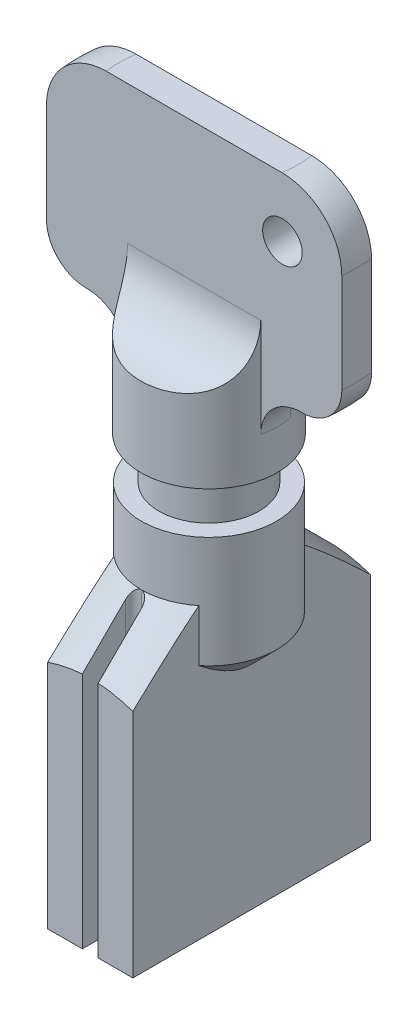
SolidWorks part; units mm, degrees
ref_plane "Front Plane" through (0, 0, 0) normal (0, 0, 1) x (1, 0, 0)
ref_plane "Top Plane" through (0, 0, 0) normal (0, 1, 0) x (1, 0, 0)
ref_plane "Right Plane" through (0, 0, 0) normal (1, 0, 0) x (0, 0, -1)
sketch "Sketch1" plane through (0, 0, 0) normal (0, 0, 1) x (1, 0, 0)
  line L0 (-3.4489, 37.7658) -> (-3.4489, 33.7658)
  line L1 (-3.4489, 33.7658) -> (-2.5348, 33.7658)
  line L2 (-2.5348, 33.7658) -> (-2.5348, 31.625)
  line L3 (-2.5348, 31.625) -> (-3.4177, 31.625)
  line L4 (-3.4177, 31.625) -> (-3.4177, 23)
  line L5 (-3.4177, 23) -> (0, 23)
  line L6 (-3.4489, 37.7658) -> (0, 37.7658)
  line L7 (0, 37.7658) -> (0, 23)
  dimension "D1" = 33.7658
  dimension "D2" = 2.1409
  dimension "D3" = 23
  dimension "D4" = 4
revolve "Revolve1" add sketch "Sketch1" angle 360 about L7
sketch "Sketch2" plane through (0, 37.7658, 0) normal (0, 1, 0) x (1, 0, 0)
  line L1 (-11.4046, 0.75) -> (11.4046, 0.75)
  line L2 (-11.4046, 0.75) -> (-11.4046, -0.75)
  line L3 (-11.4046, -0.75) -> (11.4046, -0.75)
  line L4 (11.4046, 0.75) -> (11.4046, -0.75)
  line L5 (-11.4046, 0.75) -> (11.4046, -0.75) construction
  line L6 (-11.4046, -0.75) -> (11.4046, 0.75) construction
  circle A0 centre (0, 0) radius 3.4489
  circle A1 centre (0, 0) radius 7.5
  circle M3 centre (0, 0) radius 3.4489
  dimension "D2" = 15
  dimension "D1" = 1.5
extrude "Boss-Extrude1" add sketch "Sketch2" along normal blind 10 contours L3 L1 M3 | L1 A1 L3 M3 | L3 A1 L1 M3 region at (-5.4544, 37.7658, 0) region at (0, 37.7658, 0) region at (5.4544, 37.7658, 0)
fillet "Fillet2" radius 2 4 edges at (7.5, 37.7658, 0) (-7.5, 37.7658, 0) (-3.4489, 37.7658, 0) (3.4489, 37.7658, 0)
fillet "Fillet3" radius 3 4 edges at (-7.5, 47.7658, 0) (7.5, 47.7658, 0) (0, 37.7658, -0.75) (0, 37.7658, 0.75)
sketch "Sketch3" plane through (0, 0, 0) normal (0, 0, 1) x (1, 0, 0)
  line L0 (-4.4371, 47.7658) -> (4.4371, 47.7658) construction
  line L1 (7.4624, 44.7658) -> (7.4624, 39.7658) construction
  circle A0 centre (4.4624, 44.7658) radius 1
  dimension "D1" = 2
  dimension "D2" = 3
  dimension "D3" = 3
extrude "Cut-Extrude1" cut sketch "Sketch3" against normal through all and the other way through all
sketch "Sketch4" plane through (0, 0, 0) normal (0, 0, 1) x (1, 0, 0)
  line L1 (0.4, 25.6253) -> (2.15, 25.6253)
  line L2 (0.4, 25.6253) -> (0.4, 14)
  line L3 (0.4, 14) -> (2.15, 14)
  line L4 (2.15, 25.6253) -> (2.15, 14)
  point P4 (4.2262, 13.6459)
  dimension "D1" = 2.15
  dimension "D2" = 0.4
  dimension "D3" = 14
  dimension "D4" = 1.75
extrude "Boss-Extrude2" add sketch "Sketch4" along normal blind 6 and the other way blind 6
chamfer "Chamfer1" distance 3 angle 45 2 edges at (1.3273, 25.6253, -3.1494) (1.3273, 25.6253, 3.1494)
mirror "Mirror2" about plane through (0, 0, 0) normal (1, 0, 0) of "Chamfer1", "Boss-Extrude2"
chamfer "Chamfer3" distance 3 angle 45 2 edges at (-3.4177, 23, 0) (3.4177, 23, 0)
fillet "Fillet4" radius 0.4 6 edges at (-0.4, 25.8127, -3.3942) (0.4, 25.8127, -3.3942) (-0.4, 25.8127, 3.3942) (0.4, 25.8127, 3.3942) (0.4, 23, 0) (-0.4, 23, 0)
